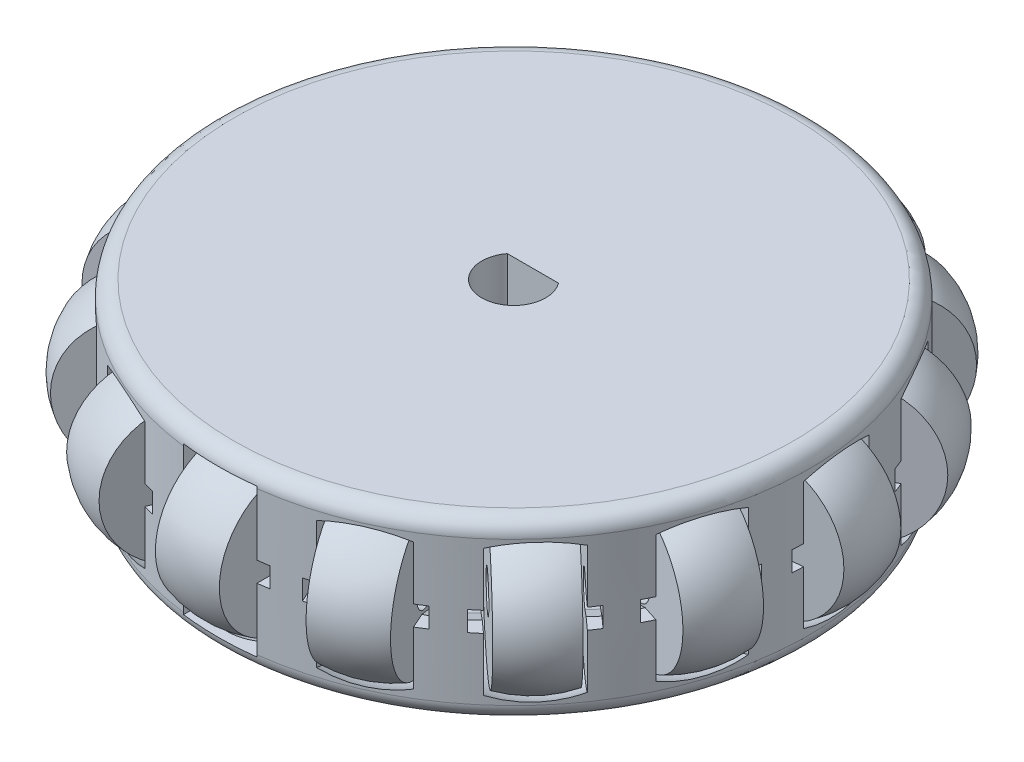
SolidWorks part; units mm, degrees
ref_plane "Front Plane" through (0, 0, 0) normal (0, 0, 1) x (1, 0, 0)
ref_plane "Top Plane" through (0, 0, 0) normal (0, 1, 0) x (1, 0, 0)
ref_plane "Right Plane" through (0, 0, 0) normal (1, 0, 0) x (0, 0, -1)
ref_axis "Axis1" through (0, -55, 0) along (0, 1, 0)
sketch "Sketch1" plane through (0, 0, 0) normal (0, 1, 0) x (1, 0, 0)
  line L0 (-1.6, 1.2) -> (1.6, 1.2)
  circle A0 centre (0, 0) radius 2
  circle A1 centre (0, 0) radius 18.5
  dimension "D1" = 4
  dimension "D2" = 37
  dimension "D3" = 1.2
extrude "Boss-Extrude1" add sketch "Sketch1" along normal mid plane 11 contours A1 A0 | L0 A0 region at (0, 0, -1.5262) region at (-17.9767, 0, 0)
sketch "Sketch3" plane through (0, 0, 0) normal (1, 0, 0) x (0, 0, -1)
  line L0 (0, 0) -> (-16, 0) construction
  dimension "D1" = 16
ref_plane "Plane1" through (0, 0, 16) normal (0, 0, 1) x (1, 0, 0)
sketch "Sketch4" plane through (0, 0, 16) normal (0, 0, 1) x (1, 0, 0)
  line L0 (-6.3455, 0) -> (8.0969, 0) construction
  line L2 (18.5, 5.5) -> (-18.5, 5.5) construction
  line L7 (2, 1.15) -> (2, 4.4082)
  line L14 (-2, 4.4082) -> (-2, 1.15)
  line L15 (-2, 1.15) -> (2, 1.15)
  line L16 (-2.3, 4.6282) -> (-2.3, 1)
  line L18 (2.3, 1) -> (2.3, 4.6282)
  line L19 (-2.3, 0.85) -> (2.3, 0.85) construction
  line L20 (-2.3, 1) -> (-3, 1)
  line L21 (-3, 1) -> (-3, 0)
  line L22 (2.3, 1) -> (3, 1)
  line L23 (3, 1) -> (3, 0)
  line L24 (-2.3, 4.6282) -> (-2.3, 0.85) construction
  line L25 (2.3, 0.85) -> (2.3, 4.6282) construction
  line L26 (-3, 0) -> (3, 0)
  arc A2 (2, 4.4082) -> (-2, 4.4082) centre (0, -2.3) ccw
  arc A3 (2.3, 4.6282) -> (-2.3, 4.6282) centre (0, -2.3) ccw
  point P17 (1.98, 1)
  point P19 (2, 4.4265)
  dimension "D4" = 6
  dimension "D6" = 2
  dimension "D7" = 0.5
  dimension "D1" = 7
  dimension "D2" = 2.3
  dimension "D3" = 0.3
  dimension "D5" = 4
revolve "Cut-Revolve1" cut sketch "Sketch4" angle 360 about L0 region at (0, 2.8779, 16) region at (0, 4.9219, 16)
sketch "Sketch5" plane through (-2.3, 0, 0) normal (1, 0, 0) x (0, 0, -1)
  line L0 (-16, 4.6282) -> (-32.0004, 4.6282)
  line L1 (-16, 6.05) -> (-16, -6.05) construction
  line L2 (-32.0004, 4.6282) -> (-32.0004, -4.6282)
  line L3 (0, 0) -> (-32.0004, 0) construction
  line L4 (-16, -4.6282) -> (-32.0004, -4.6282)
  line L5 (-16, 4.6282) -> (-16, -4.6282)
  line L6 (-16.3098, 0.9508) -> (-17.3098, 0.625)
  line L7 (-17.3098, 0.625) -> (-18.3565, 0.625)
  line L8 (-18.3565, 3.9834) -> (-18.3565, -3.9834) construction
  line L9 (-18.3565, 0.625) -> (-18.3565, 0)
  line L10 (-16.3098, 0.9508) -> (-16.3098, -0.9508)
  line L11 (-18.3565, -0.625) -> (-18.3565, 0)
  line L12 (-16.3098, -0.9508) -> (-17.3098, -0.625)
  line L13 (-17.3098, -0.625) -> (-18.3565, -0.625)
  arc A0 (-18.3565, -3.9834) -> (-18.3565, 3.9834) centre (-16, 0) ccw construction
  circle A1 centre (-16, 0) radius 1 construction
  circle A2 centre (-16, 0) radius 1 construction
  point P26 (-16.3098, 0)
  circle M11 centre (-16, 0) radius 1
  line M12 (-18.3565, 3.9834) -> (-18.3565, -3.9834)
  dimension "D1" = 1.25
  dimension "D2" = 1
extrude "Cut-Extrude3" cut sketch "Sketch5" against normal blind 0.7 contours L3 L13 L12 M11 M12 | L3 L6 L7 M11 M12 region at (-2.3, 0.3493, 17.5847) region at (-2.3, -0.3493, 17.5847)
mirror "Mirror1" about plane through (0, 0, 0) normal (1, 0, 0) of "Cut-Extrude3"
extrude "Cut-Extrude4" cut sketch "Sketch5<3>" along normal up to surface (4.6 mm away) contours L0 L2 L4 L5 up to face at (2.3, 0, 16.5463)
sketch "Sketch5<3>" plane through (-2.3, 0, 0) normal (1, 0, 0) x (0, 0, -1) same geometry as "Sketch5"
revolve "Revolve1" add sketch "Sketch4<3>" angle 360 about L0 region at (0, 2.8779, 16)
sketch "Sketch4<3>" plane through (0, 0, 16) normal (0, 0, 1) x (1, 0, 0) same geometry as "Sketch4"
pattern_circular "CirPattern6" count 15 over 360 about axis through (0, -55, 0) along (0, 1, 0) of "Cut-Revolve1", "Cut-Extrude3", "Mirror1"
pattern_circular "CirPattern7" count 15 over 360 about axis through (0, -55, 0) along (0, 1, 0) of bodies 122
fillet "Fillet1" radius 1 2 edges at (0, -5.5, 18.5) (0, 5.5, 18.5)
